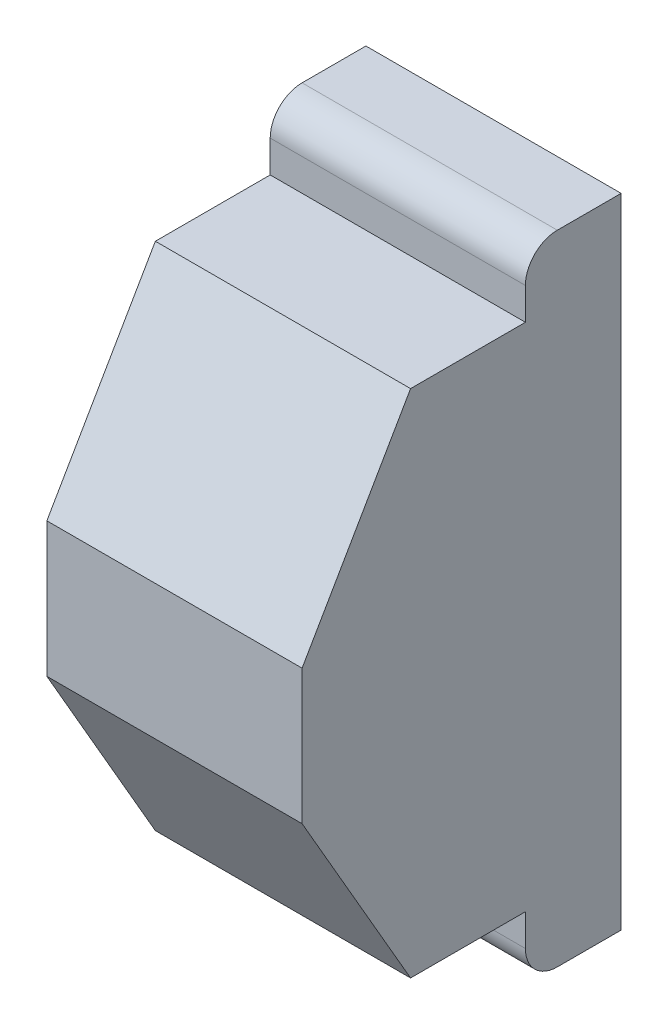
SolidWorks part; units mm, degrees
ref_plane "Front Plane" through (0, 0, 0) normal (0, 0, 1) x (1, 0, 0)
ref_plane "Top Plane" through (0, 0, 0) normal (0, 1, 0) x (1, 0, 0)
ref_plane "Right Plane" through (0, 0, 0) normal (1, 0, 0) x (0, 0, -1)
sketch "Sketch1" plane through (0, 0, 0) normal (1, 0, 0) x (0, 0, -1)
  line L0 (-1, 4) -> (1, -4) construction
  line L2 (-1, 4) -> (-1, -4) construction
  line L3 (-0.8, 4) -> (-2.5, 1.0555)
  line L4 (1, 4) -> (1, -4) construction
  line L5 (1, 4) -> (1, 5)
  line L6 (1, 5) -> (2.5, 5)
  line L7 (2.5, 5) -> (2.5, -5)
  line L8 (-4.2787, 0) -> (7.198, 0) construction
  line L9 (1, -4) -> (1, -5)
  line L10 (1, -5) -> (2.5, -5)
  line L11 (1, 4) -> (-0.8, 4)
  line L12 (-2.5, 4) -> (-2.5, -4) construction
  line L13 (-2.5, 1.0555) -> (-2.5, -1.0555)
  line L14 (-0.8, -4) -> (-2.5, -1.0555)
  line L15 (1, -4) -> (-0.8, -4)
  point P4 (0, 0)
  point P13 (2.5, 0)
  point P16 (-2.5, 0)
  point P18 (-2.5, 0)
  point P20 (-0.4264, 3)
  point P21 (-0.8462, 3)
  dimension "D1" = 2
  dimension "D2" = 8
  dimension "D3" = 1.5
  dimension "D4" = 1
  dimension "D5" = 1.5
  dimension "D6" = 60
  dimension "D7" = 0.2
extrude "Boss-Extrude1" add sketch "Sketch1" along normal blind 4
fillet "Fillet1" [suppressed] radius 2
fillet "Fillet2" radius 0.5 2 edges at (2, -5, -1) (2, 5, -1)
chamfer "Chamfer1" [suppressed] distance 1.9 angle 50
